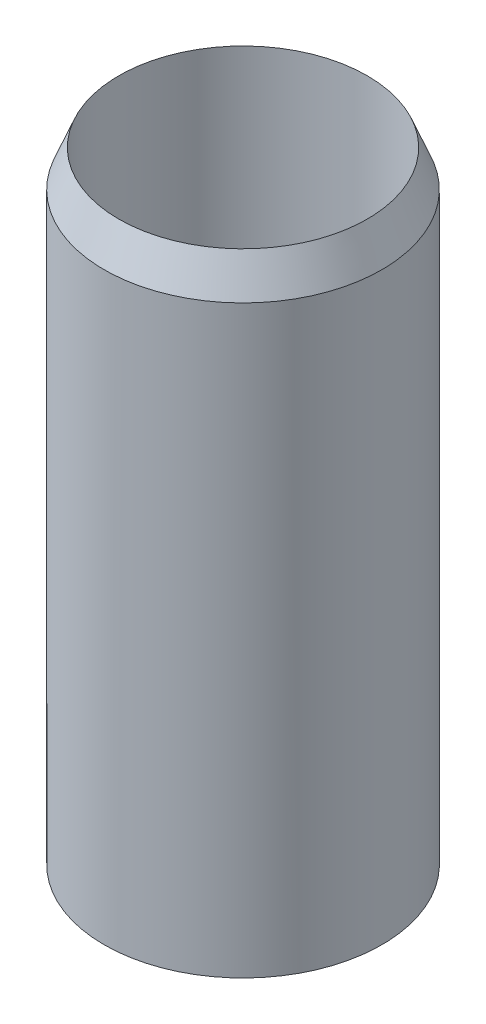
SolidWorks part; units mm, degrees
ref_plane "Спереди" through (0, 0, 0) normal (0, 0, 1) x (1, 0, 0)
ref_plane "Сверху" through (0, 0, 0) normal (0, 1, 0) x (1, 0, 0)
ref_plane "Справа" through (0, 0, 0) normal (1, 0, 0) x (0, 0, -1)
sketch "Эскиз1" plane through (0, 0, 0) normal (0, 1, 0) x (1, 0, 0)
  circle A0 centre (0, 0) radius 17
  circle A1 centre (0, 0) radius 19
  dimension "D1" = 34
  dimension "D2" = 38
extrude "Бобышка-Вытянуть1" add sketch "Эскиз1" along normal blind 80
ref_plane "Плоскость1" through (0, 85, 0) normal (0, 1, 0) x (1, 0, 0)
sketch "Эскиз2" plane through (0, 85, 0) normal (0, 1, 0) x (1, 0, 0)
  circle A0 centre (0, 0) radius 17
  dimension "D1" = 34
sketch "Эскиз3" plane through (0, 80, 0) normal (0, 1, 0) x (1, 0, 0)
  circle A0 centre (0, 0) radius 19
loft "По сечениям1" add profiles "Эскиз3", "Эскиз2" connector at (-17.3848, 80, -7.6661) connector at (-15.3674, 85, -7.2694)
sketch "Эскиз4" plane through (0, 85, 0) normal (0, 1, 0) x (1, 0, 0)
  circle A0 centre (0, 0) radius 17
extrude "Вырез-Вытянуть1" cut sketch "Эскиз4" against normal blind 5
